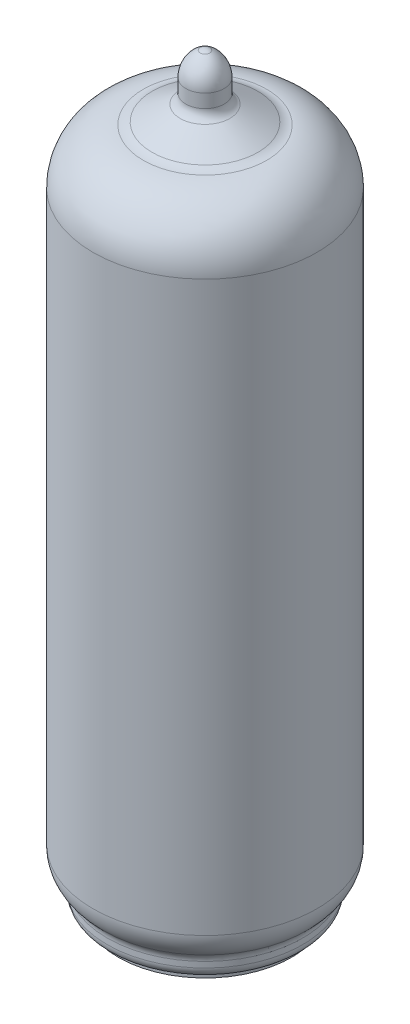
SolidWorks part; units mm, degrees
note: '?' marks a value the reader was unsure of.
material "Glass"
ref_plane "Front Plane" through (0, 0, 0) normal (0, 0, 1) x (1, 0, 0)
ref_plane "Top Plane" through (0, 0, 0) normal (0, 1, 0) x (1, 0, 0)
ref_plane "Right Plane" through (0, 0, 0) normal (1, 0, 0) x (0, 0, -1)
sketch "Sketch1" plane through (0, 0, 0) normal (0, 0, 1) x (1, 0, 0)
  line L0 (0, 93.537) -> (0, -19.6751) construction
  line L2 (0, -55) -> (0, 55) construction
  line L3 (10.25, 5) -> (10.25, 57)
  line L5 (55, 0) -> (-55, 0) construction
  line L6 (4.8423, 62.222) -> (2.2718, 63.6218)
  arc A0 (10.25, 57) -> (5.642, 61.9846) centre (5.25, 57) ccw
  arc A1 (10.25, 5) -> (8.9409, 2.5) centre (7.2083, 5) cw
  arc A2 (4.8423, 62.222) -> (5.642, 61.9846) centre (5.7988, 63.9785) ccw
  arc A3 (1.75, 64.5) -> (2.2718, 63.6218) centre (2.75, 64.5) ccw
  point P18 (5.25, 62)
  dimension "D1" = 5
  dimension "D2" = 2
  dimension "D11" = 1
  dimension "D5" = 5
  dimension "D6" = 2.5
  dimension "D9" = 57
  dimension "D12" = 7.5
revolve "Revolve-Thin1" add sketch "Sketch1" angle 360 about L0 wall 0.8
sketch "Sketch2" plane through (0, 0, 0) normal (0, 0, 1) x (1, 0, 0)
  line L0 (1.75, 64.5) -> (0.95, 64.5)
  line L2 (1.75, 64.5) -> (1.75, 65.7312)
  line L3 (1.75, 64.5) -> (-1.75, 64.5) construction
  line L4 (0.95, 64.5) -> (0.95, 64.75)
  line L5 (0, -55) -> (0, 55) construction
  line L6 (0, 68) -> (0, 65.7)
  line L7 (0, 69.2327) -> (0, 63.9562) construction
  arc A1 (0.95, 64.75) -> (0, 65.7) centre (0, 64.75) ccw
  arc A2 (0, 68) -> (0.4388, 67.8926) centre (0, 67.0502) cw
  arc A3 (0.4388, 67.8926) -> (1.75, 65.7312) centre (-0.687, 65.7312) cw
  dimension "D3" = 3.5
  dimension "D1" = 0.8
  dimension "D2" = 0.25
revolve "Revolve1" add sketch "Sketch2" angle 360 about L7
sketch "Sketch3" plane through (0, 0, 0) normal (0, 0, 1) x (1, 0, 0)
  line L0 (0, 10.7948) -> (0, -1.6521) construction
  line L1 (0, -11.275) -> (0, 11.275) construction
  line L2 (-8.9409, 2.5) -> (-8.4852, 3.1575)
  line L3 (8.4852, 3.1575) -> (-8.4852, 3.1575) construction
  line L5 (-8.4852, 3.1575) -> (0, 3.1575)
  line L6 (-8.9409, 2.5) -> (-8.9409, 1.5)
  line L7 (0, 3.1575) -> (0, 0)
  line L11 (-7.9409, 0.2753) -> (-7.9409, 0)
  line L12 (11.275, 0) -> (-11.275, 0) construction
  line L13 (-7.9409, 0) -> (0, 0)
  arc A0 (-8.1409, 0.5202) -> (-8.9409, 1.5) centre (-7.9409, 1.5) cw
  arc A1 (-7.9409, 0.2753) -> (-8.1409, 0.5202) centre (-8.1909, 0.2753) ccw
  dimension "D1" = 1
  dimension "D2" = 0.25
revolve "Revolve2" add sketch "Sketch3" angle 360 about L0
fillet "Fillet1" radius 1 1 edges at (0, 2.5, 8.9409)
fillet "Fillet2" radius 1 1 edges at (0, 3.1575, 8.4852)
ref_axis "Axis1" through (0, -3.4, 0) along (0, 1, 0)?
ref_plane "Plane1" through (0, 0, 0) normal (0.809, 0, 0.5878) x (0.5878, 0, -0.809)
sketch "Sketch4" plane through (0, 0, 0) normal (0.809, 0, 0.5878) x (0.5878, 0, -0.809)
  line L0 (-6, 12.5047) -> (-6, -2.8504) construction
  line L1 (0, -3.4) -> (0, 71.4) construction
  line L2 (-6.5331, 5) -> (-6, 5)
  line L3 (-6, 5) -> (-6, 0)
  line L4 (-6, 0) -> (-7.4, 0)
  line L5 (-7.9409, 0) -> (7.9409, 0) construction
  line L6 (-7.4, 0) -> (-7.4, 3.2568)
  line L8 (-7.2852, 3.8324) -> (-6.9024, 4.7535)
  line L9 (11.275, 0) -> (-11.275, 0) construction
  arc A0 (-7.4, 3.2568) -> (-7.2852, 3.8324) centre (-5.9, 3.2568) cw
  arc A1 (-6.9024, 4.7535) -> (-6.5331, 5) centre (-6.5331, 4.6) cw
  point P17 (-6.8, 5)
  dimension "D2" = 1.5
  dimension "D6" = 0.4
  dimension "D1" = 6
  dimension "D3" = 0.8
  dimension "D4" = 5
  dimension "D5" = 1.4
revolve "Revolve3" add sketch "Sketch4" angle 360 about L0
pattern_circular "CirPattern1" count 9 every 36 about axis through (0, 0, 0) along (0, 1, 0) of "Revolve3"
